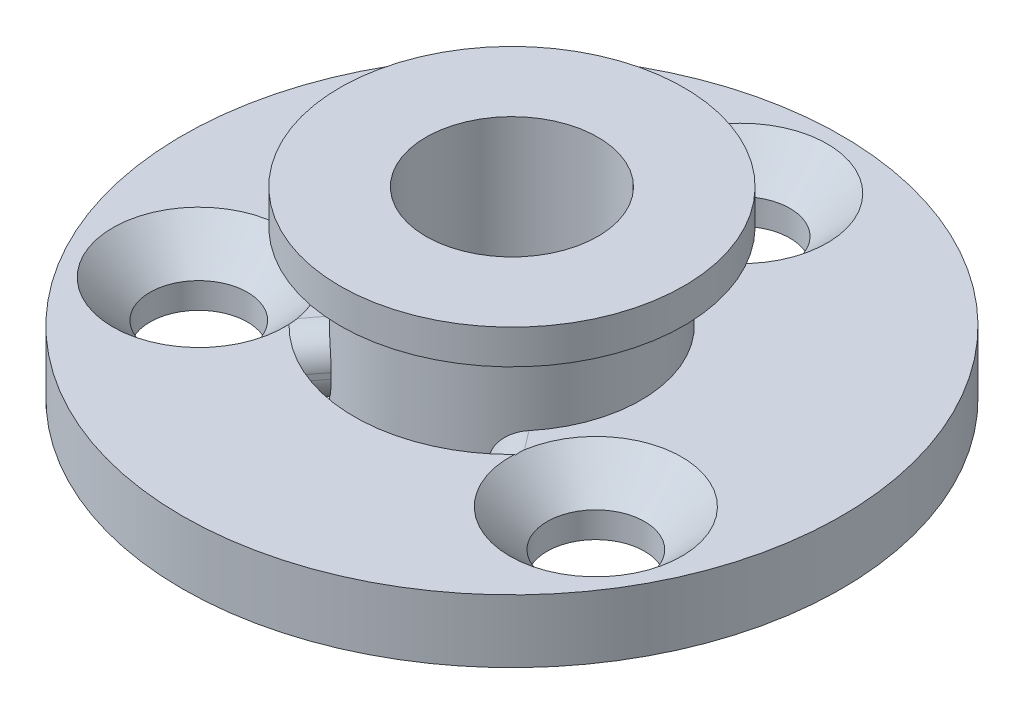
SolidWorks part; units mm, degrees
ref_plane "Plan de face" through (0, 0, 0) normal (0, 0, 1) x (1, 0, 0)
ref_plane "Plan de dessus" through (0, 0, 0) normal (0, 1, 0) x (1, 0, 0)
ref_plane "Plan de droite" through (0, 0, 0) normal (1, 0, 0) x (0, 0, -1)
sketch "Esquisse1" plane through (0, 0, 0) normal (0, 0, 1) x (1, 0, 0)
  line L0 (0, 4.6899) -> (0, -3.9873) construction
  line L1 (3, -3.2) -> (3, 3.2)
  line L2 (3, 3.2) -> (6, 3.2)
  line L3 (6, 3.2) -> (6, 2)
  line L4 (6, 2) -> (4.5, 2)
  line L5 (4.5, 2) -> (4.5, -1)
  line L6 (4.5, -1) -> (11.5, -1)
  line L7 (11.5, -1) -> (11.5, -3.2)
  line L8 (11.5, -3.2) -> (3, -3.2)
  point P5 (4.5, 0.5)
  point P12 (3, 0)
  dimension "D1" = 1.2
  dimension "D2" = 2.2
  dimension "D3" = 3
  dimension "D4" = 3
  dimension "D5" = 1.5
  dimension "D6" = 1.5
  dimension "D7" = 11.5
revolve "Révolution1" add sketch "Esquisse1" angle 360 about L0
sketch "Esquisse2" plane through (0, -1, 0) normal (0, 1, 0) x (1, 0, 0)
  line L0 (0, 0) -> (0, 8) construction
  line L1 (0, 0) -> (6.9282, -4) construction
  line L2 (0, 0) -> (-6.9282, -4) construction
  circle A0 centre (0, 0) radius 8 construction
  circle A1 centre (0, 8) radius 1.7 construction
  circle A2 centre (0, 8) radius 2.85 construction
  circle A3 centre (6.9282, -4) radius 2.85 construction
  circle A4 centre (6.9282, -4) radius 1.7 construction
  circle A5 centre (-6.9282, -4) radius 2.85 construction
  circle A6 centre (-6.9282, -4) radius 1.7 construction
  point P14 (0, 0)
  dimension "D1" = 16
  dimension "D2" = 3.4
  dimension "D3" = 5.7
  dimension "D4" = 3
sketch "Esquisse5" plane through (0, -1, 0) normal (0, 1, 0) x (1, 0, 0)
  point P0 (-6.9282, -4)
  point P3 (6.9282, -4)
  point P6 (0, 8)
hole_wizard "CSK for M3 Flat Head Machine Screw1" positions "Esquisse5" profile "Esquisse4" countersink size "M3" standard "ANSI Metric" end condition through all
sketch "Esquisse4" plane through (-6.9282, -1, 4) normal (1, 0, 0) x (0, 0, 1)
  line L0 (0, 0) -> (0, 2.2)
  line L1 (0, 2.2) -> (1.7, 2.2)
  line L2 (1.7, 2.2) -> (1.7, 1.3)
  line L3 (1.7, 1.3) -> (3, 0)
  line L5 (3, 0) -> (0, 0)
  line L6 (-1.7, 1.3) -> (-3, 0) construction
  line L11 (0, -6.35) -> (0, 107.95) construction
  dimension "Thru Hole Dia." = 3.4
  dimension "Thru Hole Depth" = 2.2
  dimension "Near C'Sink Dia." = 6
  dimension "Near C'Sink Angle" = 90
sketch "Esquisse6" plane through (0, -1, 0) normal (0, 1, 0) x (1, 0, 0)
  line L0 (2.7394, -3.5701) -> (3.3482, -4.3634)
  line L1 (-2.7394, -3.5701) -> (-3.3482, -4.3634)
  line L2 (0, 0) -> (0, -11.5) construction
  arc A0 (2.7394, -3.5701) -> (-2.7394, -3.5701) centre (0, 0) cw
  arc A1 (-3.3482, -4.3634) -> (3.3482, -4.3634) centre (0, 0) ccw
  circle A2 centre (0, 0) radius 4.5 construction
  circle A3 centre (0, 0) radius 11.5 construction
  dimension "D1" = 1
  dimension "D2" = 37.5
  dimension "D3" = 37.5
extrude "Enlèv. mat.-Extru.1" cut sketch "Esquisse6" against normal through all
fillet "Congé1" radius 1 4 edges at (3.0438, -3.2, 3.9668) (-3.0438, -3.2, 3.9668) (-3.0438, -1, 3.9668) (3.0438, -1, 3.9668)
